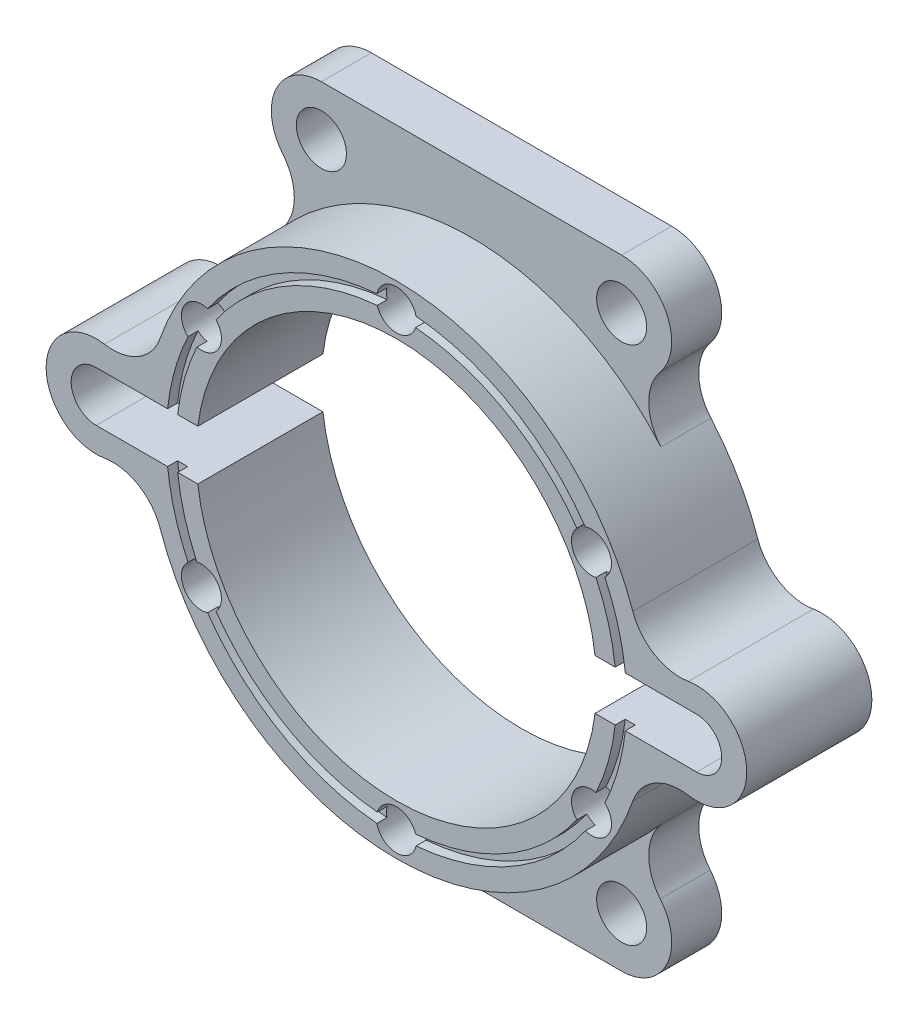
SolidWorks part; units mm, degrees
material "AISI 4130 Steel, normalized at 870C"
ref_plane "Front Plane" through (0, 0, 0) normal (0, 0, 1) x (1, 0, 0)
ref_plane "Top Plane" through (0, 0, 0) normal (0, 1, 0) x (1, 0, 0)
ref_plane "Right Plane" through (0, 0, 0) normal (1, 0, 0) x (0, 0, -1)
sketch "Sketch2" plane through (0, 0, 0) normal (0, 0, 1) x (1, 0, 0)
  line L0 (-39.6863, 5) -> (-60, 5)
  line L1 (77, 0) -> (-77, 0) construction
  line L2 (-39.6863, -5) -> (-60, -5)
  line L3 (-30, 61.9615) -> (30, 61.9615)
  line L4 (0, 0) -> (-30, 51.9615) construction
  line L5 (0, 0) -> (0, 61.9615) construction
  line L6 (-30, -61.9615) -> (30, -61.9615)
  line L7 (0, -68.1577) -> (0, 68.1577) construction
  line L8 (39.6863, -5) -> (60, -5)
  line L9 (39.6863, 5) -> (60, 5)
  arc A0 (-36.0477, -25.2301) -> (-3.8261, -43.8333) centre (0, 0) ccw
  arc A1 (-39.6863, -5) -> (39.6863, -5) centre (0, 0) ccw
  arc A2 (-36.8192, -25.8718) -> (-3.996, -44.8222) centre (0, 0) ccw construction
  arc A3 (-37.7367, -26.3048) -> (-3.9122, -45.8333) centre (0, 0) ccw
  arc A4 (-47.2222, -16.4336) -> (47.2222, -16.4336) centre (0, 0) ccw
  circle A5 centre (0, 0) radius 60 construction
  circle A6 centre (0, 45) radius 4
  circle A7 centre (30, 51.9615) radius 5
  circle A8 centre (-30, 51.9615) radius 5
  arc A9 (-60, 5) -> (-60, -5) centre (-60, 0) ccw
  arc A10 (-58.3333, 9.8601) -> (-58.3333, -9.8601) centre (-60, 0) ccw
  arc A11 (-58.3333, 9.8601) -> (-47.2222, 16.4336) centre (-56.6667, 19.7203) ccw
  arc A12 (-37.843, 32.6789) -> (-37.7058, 45.5881) centre (-45.4116, 39.2146) ccw
  arc A13 (-37.7058, 45.5881) -> (-30, 61.9615) centre (-30, 51.9615) cw
  arc A14 (30, 61.9615) -> (37.7058, 45.5881) centre (30, 51.9615) cw
  arc A15 (37.7058, 45.5881) -> (37.843, 32.6789) centre (45.4116, 39.2146) ccw
  circle A16 centre (38.9711, 22.5) radius 4
  circle A17 centre (38.9711, -22.5) radius 4
  circle A18 centre (0, -45) radius 4
  circle A19 centre (-38.9711, -22.5) radius 4
  circle A20 centre (-38.9711, 22.5) radius 4
  arc A21 (3.8261, -43.8333) -> (36.0477, -25.2301) centre (0, 0) ccw
  arc A22 (3.996, -44.8222) -> (36.8192, -25.8718) centre (0, 0) ccw construction
  arc A23 (3.9122, -45.8333) -> (37.7367, -26.3048) centre (0, 0) ccw
  arc A24 (39.8738, -18.6032) -> (43.715, -5) centre (0, 0) ccw
  arc A25 (40.8152, -18.9504) -> (44.7214, -5) centre (0, 0) ccw construction
  arc A26 (41.6489, -19.5286) -> (45.7275, -5) centre (0, 0) ccw
  arc A27 (37.7367, 26.3048) -> (3.9122, 45.8333) centre (0, 0) ccw
  arc A28 (36.8192, 25.8718) -> (3.996, 44.8222) centre (0, 0) ccw construction
  arc A29 (36.0477, 25.2301) -> (3.8261, 43.8333) centre (0, 0) ccw
  arc A30 (-3.9122, 45.8333) -> (-37.7367, 26.3048) centre (0, 0) ccw
  arc A31 (-3.996, 44.8222) -> (-36.8192, 25.8718) centre (0, 0) ccw construction
  arc A32 (-3.8261, 43.8333) -> (-36.0477, 25.2301) centre (0, 0) ccw
  arc A33 (-39.8738, 18.6032) -> (-43.715, 5) centre (0, 0) ccw
  arc A34 (-40.8152, 18.9504) -> (-44.7214, 5) centre (0, 0) ccw construction
  arc A35 (-41.6489, 19.5286) -> (-45.7275, 5) centre (0, 0) ccw
  arc A36 (-43.715, -5) -> (-39.8738, -18.6032) centre (0, 0) ccw
  arc A37 (-44.7214, -5) -> (-40.8152, -18.9504) centre (0, 0) ccw construction
  arc A38 (-45.7275, -5) -> (-41.6489, -19.5286) centre (0, 0) ccw
  arc A39 (37.7058, -45.5881) -> (37.843, -32.6789) centre (45.4116, -39.2146) cw
  arc A40 (30, -61.9615) -> (37.7058, -45.5881) centre (30, -51.9615) ccw
  circle A41 centre (30, -51.9615) radius 5
  circle A42 centre (-30, -51.9615) radius 5
  arc A43 (-37.7058, -45.5881) -> (-30, -61.9615) centre (-30, -51.9615) ccw
  arc A44 (-37.843, -32.6789) -> (-37.7058, -45.5881) centre (-45.4116, -39.2146) cw
  arc A45 (-58.3333, -9.8601) -> (-47.2222, -16.4336) centre (-56.6667, -19.7203) cw
  arc A46 (58.3333, 9.8601) -> (47.2222, 16.4336) centre (56.6667, 19.7203) cw
  arc A47 (58.3333, -9.8601) -> (47.2222, -16.4336) centre (56.6667, -19.7203) ccw
  arc A48 (58.3333, 9.8601) -> (58.3333, -9.8601) centre (60, 0) cw
  arc A49 (60, 5) -> (60, -5) centre (60, 0) cw
  arc A50 (39.6863, 5) -> (-39.6863, 5) centre (0, 0) ccw
  arc A51 (43.715, 5) -> (39.8738, 18.6032) centre (0, 0) ccw
  arc A52 (44.7214, 5) -> (40.8152, 18.9504) centre (0, 0) ccw construction
  arc A53 (45.7275, 5) -> (41.6489, 19.5286) centre (0, 0) ccw
  arc A54 (47.2222, 16.4336) -> (-47.2222, 16.4336) centre (0, 0) ccw
  point P10 (0, 0)
  point P16 (0, 0)
  point P38 (0, 61.9615)
  point P101 (0, 0)
  dimension "D1" = 80
  dimension "D2" = 100
  dimension "D3" = 90
  dimension "D4" = 92
  dimension "D5" = 88
  dimension "D6" = 120
  dimension "D7" = 10
  dimension "D9" = 10
  dimension "0" = 10
  dimension "D10" = 10
  dimension "D11" = 10
  dimension "D12" = 5
  dimension "D13" = 8
  dimension "D8" = 30
  dimension "D14" = 6
extrude "Boss-Extrude1" add sketch "Sketch2" along normal blind 10 contours A54 A15 A14 L3 A13 A12 A8 A7 | A4 A44 A43 L6 A40 A39 A42 A41 region at (0, 53.0646, 0) region at (0, -53.0646, 0)
extrude "Boss-Extrude2" add sketch "Sketch2<3>" along normal blind 25 contours A46 A54 A11 A10 A45 A4 A47 A48 A53 L9 A49 L8 A26 A17 A23 A18 A3 A19 A38 L2 A9 L0 A35 A20 A30 A6 A27 A16 | L9 A51 A16 A29 A6 A32 A20 A33 L0 A50 | L2 A36 A19 A0 A18 A21 A17 A24 L8 A1 region at (-41.7006, 5.9567, 0) region at (-41.7006, -5.9567, 0) region at (0, 49.828, 0)
sketch "Sketch2<3>" plane through (0, 0, 0) normal (0, 0, 1) x (1, 0, 0) same geometry as "Sketch2"
extrude "Boss-Extrude3" add sketch "Sketch2<4>" along normal blind 23 contours L2 A38 A19 A36 | A19 A3 A18 A0 | A18 A23 A17 A21 | A17 A26 L8 A24 | L9 A53 A16 A51 | A29 A16 A27 A6 | A32 A6 A30 A20 | A20 A35 L0 A33 region at (-43.1486, 12.1032, 0) region at (43.1486, 12.1032, 0) region at (-22.8016, 39.4935, 0) region at (22.1984, 38.4487, 0) region at (-43.1486, -12.1032, 0) region at (43.1486, -12.1032, 0) region at (-36.6109, -26.2096, 0) region at (4.3726, -45.4605, 0)
sketch "Sketch2<4>" plane through (0, 0, 0) normal (0, 0, 1) x (1, 0, 0) same geometry as "Sketch2"
